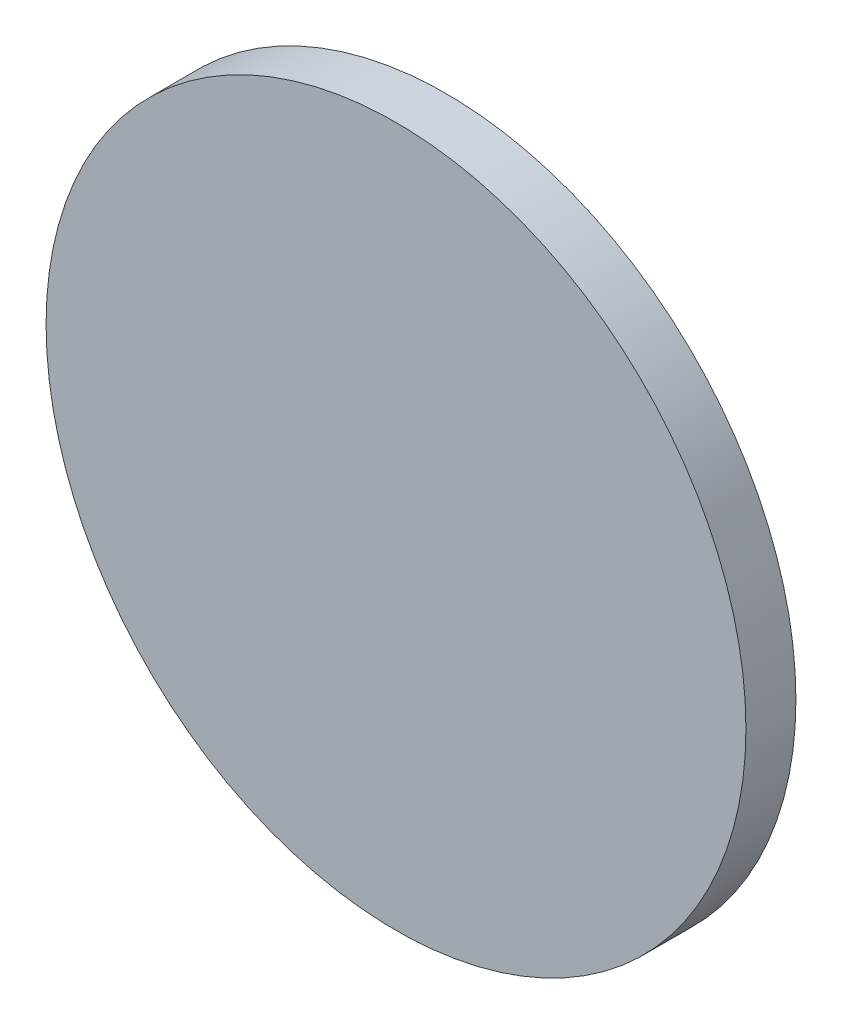
SolidWorks part; units mm, degrees
material "Acrylic (Medium-high impact)"
ref_plane "Front Plane" through (0, 0, 0) normal (0, 0, 1) x (1, 0, 0)
ref_plane "Top Plane" through (0, 0, 0) normal (0, 1, 0) x (1, 0, 0)
ref_plane "Right Plane" through (0, 0, 0) normal (1, 0, 0) x (0, 0, -1)
sketch "Sketch1" plane through (0, 0, 0) normal (0, 0, 1) x (1, 0, 0)
  circle A0 centre (0, 0) radius 22.225
  dimension "D1" = 44.45
extrude "Boss-Extrude1" add sketch "Sketch1" along normal blind 3.175
